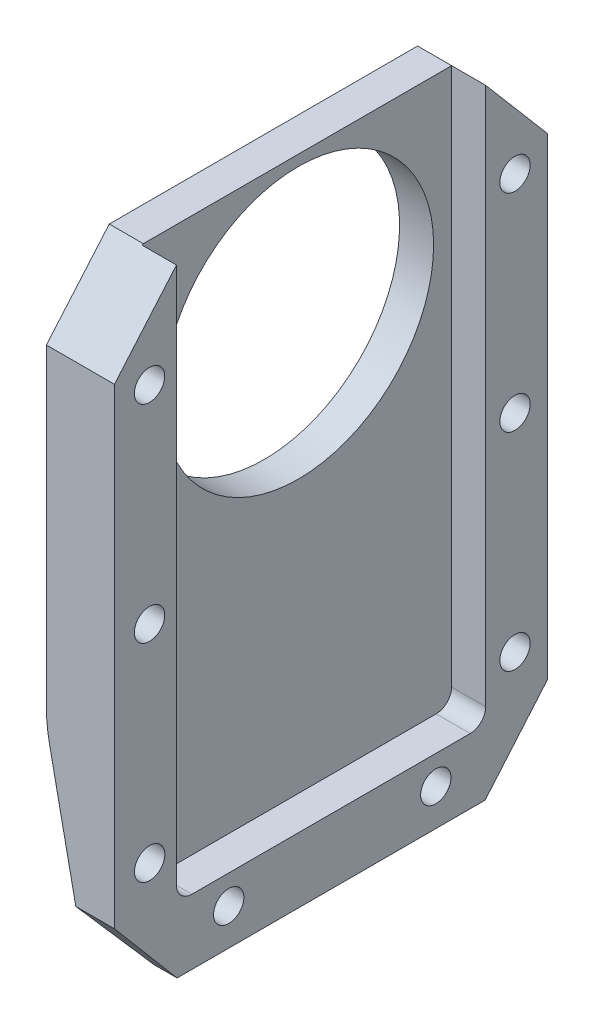
SolidWorks part; units mm, degrees
material "PLA"
ref_plane "Front Plane" through (0, 0, 0) normal (0, 0, 1) x (1, 0, 0)
ref_plane "Top Plane" through (0, 0, 0) normal (0, 1, 0) x (1, 0, 0)
ref_plane "Right Plane" through (0, 0, 0) normal (1, 0, 0) x (0, 0, -1)
sketch "Sketch1" plane through (0, 0, 0) normal (0, 0, 1) x (1, 0, 0)
  line L0 (0, 0) -> (0, 50.8)
  line L1 (0, 50.8) -> (-5.588, 50.8)
  line L2 (-5.588, 50.8) -> (-5.588, 17.78)
  line L3 (-5.588, 17.78) -> (-1.9166, 0)
  line L4 (-1.9166, 0) -> (0, 0)
extrude "Boss-Extrude1" add sketch "Sketch1" along normal blind 35.56
fillet "Fillet1" radius 12.7 1 edges at (-5.588, 17.78, 17.78)
sketch "Sketch6" plane through (0, 0, 0) normal (1, 0, 0) x (0, 0, -1)
  line L0 (-17.78, 50.8) -> (-17.78, 0) construction
  line L1 (-35.56, 50.8) -> (0, 50.8) construction
  line L2 (-35.56, 0) -> (0, 0) construction
  line L3 (-17.78, -971.6385) -> (-17.78, 49028.3615) construction
  line L4 (-30.47, 50.8) -> (-5.086, 50.8)
  line L5 (-30.47, 50.8) -> (-30.47, 5.35)
  line L6 (-30.47, 5.35) -> (-5.086, 5.35)
  line L7 (-5.086, 50.8) -> (-5.086, 5.35)
  dimension "D1" = 45.45
  dimension "D2" = 25.384
  dimension "D3" = 12.69
  dimension "0" = 0
extrude "Cut-Extrude1" cut sketch "Sketch6" against normal blind 2.794
fillet "Fillet2" radius 1.27 2 edges at (-1.397, 5.35, 30.47) (-1.397, 5.35, 5.086)
sketch "Sketch10" plane through (0, 0, 0) normal (1, 0, 0) x (0, 0, -1)
  line L0 (-35.56, 44.7804) -> (-30.3976, 50.8)
  line L1 (-35.56, 0) -> (-35.56, 50.8) construction
  line L2 (-35.56, 50.8) -> (-30.47, 50.8) construction
  line L3 (-30.3976, 50.8) -> (-35.56, 50.8)
  line L4 (-35.56, 50.8) -> (-35.56, 44.7804)
extrude "Cut-Extrude3" cut sketch "Sketch10" against normal through all
sketch "Sketch11" plane through (0, 0, 0) normal (1, 0, 0) x (0, 0, -1)
  line L0 (-5.0855, 50.8) -> (0, 50.8)
  line L1 (-5.086, 50.8) -> (0, 50.8) construction
  line L2 (0, 50.8) -> (0, 44.8249)
  line L3 (0, 0) -> (0, 50.8) construction
  line L4 (0, 44.8249) -> (-5.0855, 50.8)
  line L5 (0, 6.0295) -> (-5.1287, 0)
  line L6 (-35.56, 0) -> (0, 0) construction
  line L7 (-5.1287, 0) -> (0, 0)
  line L8 (0, 0) -> (0, 6.0295)
  line L9 (-35.56, 6.0712) -> (-35.56, 0)
  line L10 (-35.56, 0) -> (-35.56, 44.7804) construction
  line L11 (-35.56, 0) -> (-30.4171, 0)
  line L12 (-30.4171, 0) -> (-35.56, 6.0712)
extrude "Cut-Extrude4" cut sketch "Sketch11" against normal through all
hole_wizard "7/8 (0.875) Diameter Hole1" positions "Sketch12" profile "Sketch13" hole size "7/8" standard "ANSI Inch" end condition through all
sketch "Sketch12" plane through (-5.588, 0, 0) normal (-1, 0, 0) x (0, 0, 1)
  point P0 (17.6785, 38.8095)
sketch "Sketch13" plane through (-5.588, 38.8095, 17.6785) normal (0, 1, 0) x (0, 0, 1)
  line L0 (0, 0) -> (0, 5.588)
  line L1 (0, 5.588) -> (11.1125, 5.588)
  line L2 (11.1125, 5.588) -> (11.1125, 0)
  line L5 (11.1125, 0) -> (0, 0)
  line L11 (0, -6.35) -> (0, 107.95) construction
  dimension "Thru Hole Dia." = 22.225
  dimension "Thru Hole Depth" = 5.588
hole_wizard "#40 (0.098) Diameter Hole1" positions "Sketch14" profile "Sketch15" hole size "#40" standard "ANSI Inch" end condition through all
sketch "Sketch14" plane through (-5.588, 0, 0) normal (-1, 0, 0) x (0, 0, 1)
  point P0 (2.6785, 43.3095)
  point P3 (2.6785, 26.3095)
  point P6 (2.6785, 9.3095)
  point P9 (9.1785, 3.0095)
  point P12 (26.1819, 2.9992)
  point P14 (32.6729, 9.2992)
  point P16 (32.6785, 26.3095)
  point P19 (32.6785, 43.2992)
sketch "Sketch15" plane through (-5.588, 43.3095, 2.6785) normal (0, 1, 0) x (0, 0, 1)
  line L0 (0, 0) -> (0, 5.588)
  line L1 (0, 5.588) -> (1.2446, 5.588)
  line L2 (1.2446, 5.588) -> (1.2446, 0.635)
  line L3 (1.2446, 0.635) -> (1.8796, 0)
  line L5 (1.8796, 0) -> (0, 0)
  line L6 (-1.2446, 0.635) -> (-1.8796, 0) construction
  line L11 (0, -6.35) -> (0, 107.95) construction
  dimension "Thru Hole Dia." = 2.4892
  dimension "Thru Hole Depth" = 5.588
  dimension "Near C'Sink Dia." = 3.7592
  dimension "Near C'Sink Angle" = 90
sketch "Sketch17" plane through (-5.588, 0, 0) normal (-1, 0, 0) x (0, 0, 1)
  line L0 (6.566, 38.8095) -> (28.791, 38.8095) construction
  circle A0 centre (17.6785, 38.8095) radius 11.1125 construction
  circle A1 centre (17.6785, 38.8095) radius 11.1125
  point P7 (17.6785, 38.8095)
